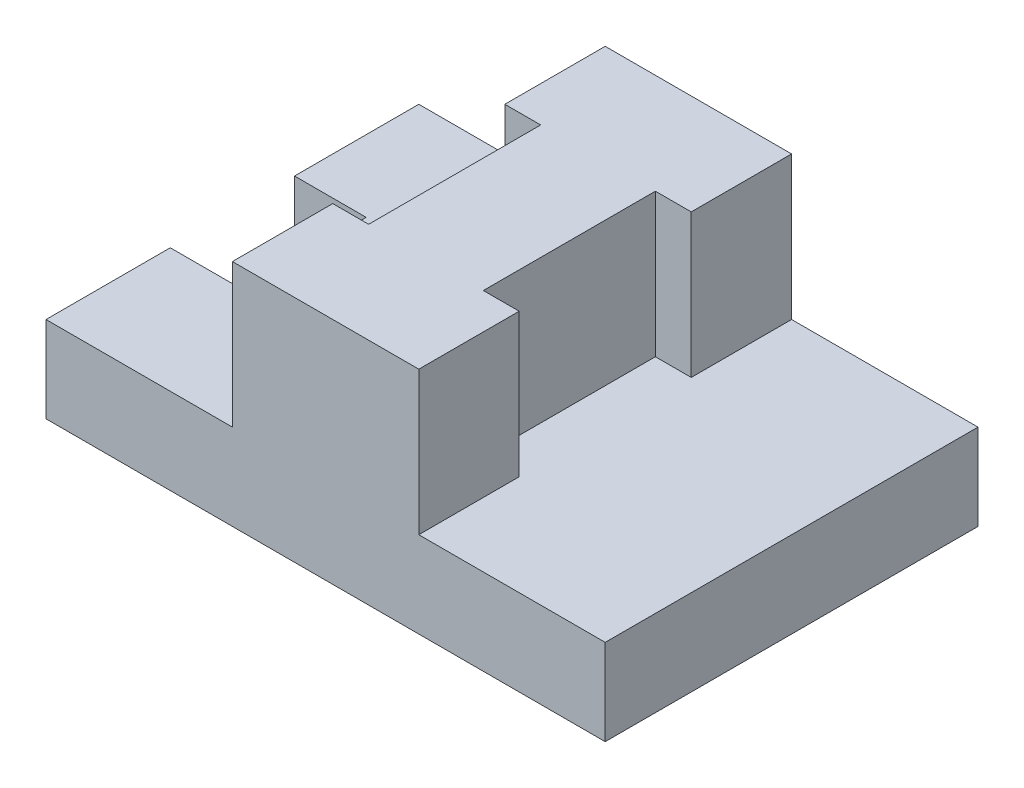
SolidWorks part; units mm, degrees
ref_plane "Front Plane" through (0, 0, 0) normal (0, 0, 1) x (1, 0, 0)
ref_plane "Top Plane" through (0, 0, 0) normal (0, 1, 0) x (1, 0, 0)
ref_plane "Right Plane" through (0, 0, 0) normal (1, 0, 0) x (0, 0, -1)
sketch "Sketch6" plane through (0, 0, 0) normal (0, 1, 0) x (1, 0, 0)
  line L0 (-52.7598, 29.976) -> (-52.7598, 12.6427)
  line L1 (-52.7598, 12.6427) -> (-42.7598, 12.6427)
  line L2 (-42.7598, 12.6427) -> (-42.7598, -4.6907)
  line L3 (-42.7598, -4.6907) -> (-52.7598, -4.6907)
  line L4 (-52.7598, -4.6907) -> (-52.7598, -22.024)
  line L5 (-52.7598, -22.024) -> (25.2402, -22.024)
  line L6 (25.2402, -22.024) -> (25.2402, 29.976)
  line L7 (25.2402, 29.976) -> (-52.7598, 29.976)
  line L8 (-52.7598, -22.024) -> (-26.7598, -22.024)
  line L9 (-26.7598, -22.024) -> (-26.7598, -8.024)
  line L10 (-26.7598, -8.024) -> (-21.7598, -8.024)
  line L11 (-21.7598, -8.024) -> (-21.7598, 15.976)
  line L12 (-21.7598, 15.976) -> (-26.7598, 15.976)
  line L13 (-26.7598, 15.976) -> (-26.7598, 29.976)
  line L14 (-26.7598, -22.024) -> (-0.7598, -22.024)
  line L15 (-0.7598, -22.024) -> (-0.7598, -8.024)
  line L16 (-0.7598, -8.024) -> (-5.7598, -8.024)
  line L17 (-5.7598, -8.024) -> (-5.7598, 15.976)
  line L18 (-5.7598, 15.976) -> (-0.7598, 15.976)
  line L19 (-0.7598, 15.976) -> (-0.7598, 29.976)
extrude "Boss-Extrude5" add sketch "Sketch6" along normal blind 12 contours L12 L13 L7 L0 L1 L2 L3 L4 L5 L9 L10 L11 | L19 L18 L17 L16 L15 L5 L6 L7 region at (-37.2598, 0, -3.976) region at (10.9766, 0, -3.976)
extrude "Boss-Extrude6" add sketch "Sketch6<3>" along normal blind 32 contours L18 L19 L7 L13 L12 L11 L10 L9 L5 L15 L16 L17 region at (-13.7598, 0, -3.976)
sketch "Sketch6<3>" plane through (0, 0, 0) normal (0, 1, 0) x (1, 0, 0) same geometry as "Sketch6"
